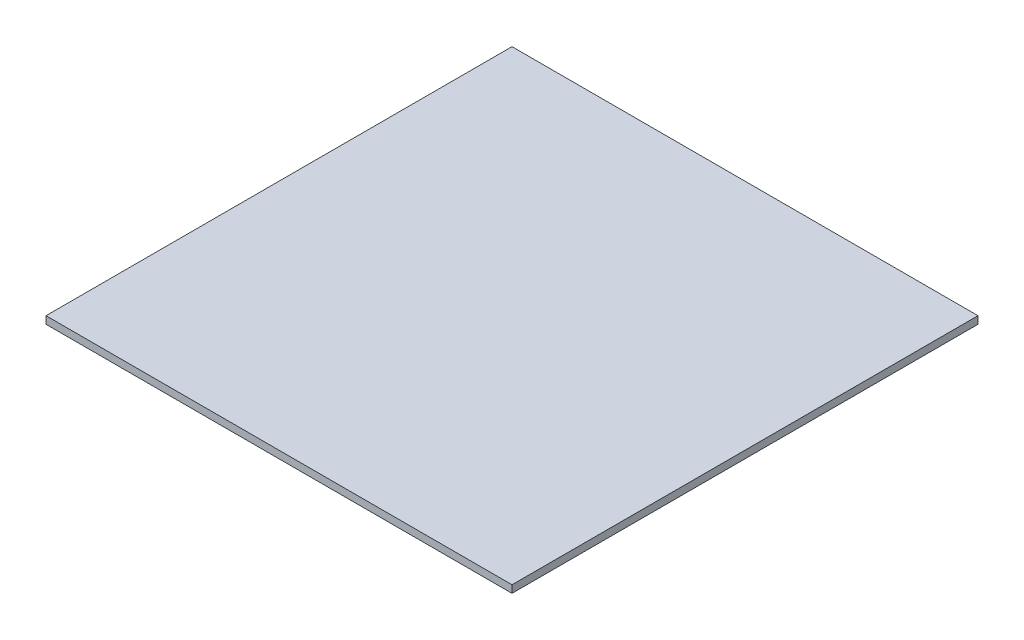
SolidWorks part; units mm, degrees
ref_plane "Front Plane" through (0, 0, 0) normal (0, 0, 1) x (1, 0, 0)
ref_plane "Top Plane" through (0, 0, 0) normal (0, 1, 0) x (1, 0, 0)
ref_plane "Right Plane" through (0, 0, 0) normal (1, 0, 0) x (0, 0, -1)
sketch "Sketch1" plane through (0, 0, 0) normal (0, 1, 0) x (1, 0, 0)
  line L1 (0, 0) -> (250, 0)
  line L2 (0, 0) -> (0, -250)
  line L3 (0, -250) -> (250, -250)
  line L4 (250, 0) -> (250, -250)
  line L5 (0, 0) -> (250, -250) construction
  line L6 (0, -250) -> (250, 0) construction
  point P4 (125, -125)
  dimension "D1" = 250
  dimension "D2" = 250
extrude "Boss-Extrude1" add sketch "Sketch1" along normal blind 4
